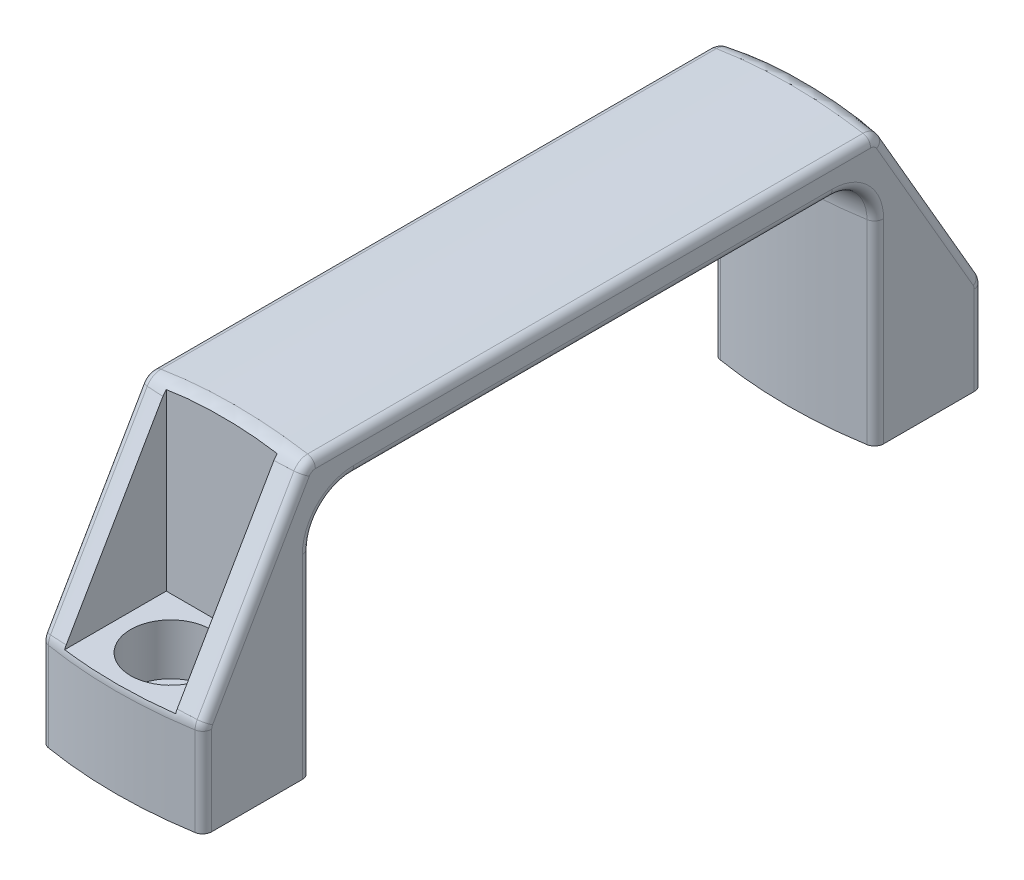
SolidWorks part; units mm, degrees
material "Nylon 6/10"
ref_plane "Front Plane" through (0, 0, 0) normal (0, 0, 1) x (1, 0, 0)
ref_plane "Top Plane" through (0, 0, 0) normal (0, 1, 0) x (1, 0, 0)
ref_plane "Right Plane" through (0, 0, 0) normal (1, 0, 0) x (0, 0, -1)
ref_axis "Axis1" through (0, 0, -88.99) along (0, 0, 1)
ref_axis "Axis2" through (0, -55, 0) along (0, 1, 0)
ref_axis "Axis3" through (-88.99, 0, 0) along (1, 0, 0)
sketch "Sketch1" plane through (0, 0, 0) normal (1, 0, 0) x (0, 0, -1)
  line L0 (-54.3719, 0) -> (-37.8312, 0)
  line L1 (-37.8312, 0) -> (-37.8312, 31.75)
  line L2 (-37.8312, 31.75) -> (0, 31.75)
  line L3 (0, 31.75) -> (0, 38.1)
  line L4 (0, 38.1) -> (-39.8313, 38.1)
  line L5 (-54.3719, 0) -> (-54.3719, 13)
  line L6 (-54.3719, 13) -> (-39.8313, 38.1)
  line L7 (-46.8313, 26.0166) -> (-46.8313, 0) construction
  line L8 (0, 0) -> (0, 31.75) construction
  line L9 (-49.8313, 20.838) -> (-49.8312, 0) construction
  line L10 (-43.8313, 31.1952) -> (-43.8313, 0) construction
  line L11 (-39.8313, 38.1) -> (-39.8313, 13)
  line L12 (-39.8313, 13) -> (-54.3719, 13)
  dimension "D1" = 6.35
  dimension "D2" = 38.1
  dimension "D3" = 93.6625
  dimension "D4" = 108.7438
  dimension "D5" = 6
  dimension "D6" = 13
  dimension "D7" = 2
  dimension "D8" = 4
extrude "Boss-Extrude1" add sketch "Sketch1" along normal mid plane 22.225 contours L11 L12 L5 L0 L1 L2 L3 L4 | L12 L11 L6 region at (0, 6.5, 53.708) region at (0, 21.3667, 44.6781)
extrude "Cut-Extrude1" cut sketch "Sketch1<3>" along normal offset from surface 3.5 and the other way offset from surface 3.5 contours L12 L11 L6 region at (0, 21.3667, 44.6781) up to face at (11.1125, 21.8143, 32.0339) other way up to face at (-11.1125, 21.8143, 32.0339)
sketch "Sketch1<3>" plane through (0, 0, 0) normal (1, 0, 0) x (0, 0, -1) same geometry as "Sketch1"
fillet "Fillet1" radius 5 1 edges at (0, 31.75, 37.8312)
hole_wizard "CBORE for  SHCS1" positions "Sketch3" profile "Sketch2" counterbore size "M6" standard "ANSI Metric" end condition through all
sketch "Sketch3" plane through (0, 13, 0) normal (0, 1, 0) x (1, 0, 0)
  point P0 (0, -46.8313)
sketch "Sketch2" plane through (0, 13, 46.8313) normal (1, 0, 0) x (0, 0, 1)
  line L0 (0, 0) -> (0, 13)
  line L1 (0, 13) -> (3.2, 13)
  line L3 (3.2, 13) -> (3.2, 7)
  line L4 (3.2, 7) -> (5.5, 7)
  line L5 (5.5, 7) -> (5.5, 0)
  line L7 (5.5, 0) -> (0, 0)
  line L11 (0, -6.35) -> (0, 107.95) construction
  dimension "Thru Hole Dia." = 6.4
  dimension "Thru Hole Depth" = 13
  dimension "C'Bore Dia." = 11
  dimension "C'Bore Depth" = 7
sketch "Sketch4" plane through (0, 0, 0) normal (0, 0, -1) x (-1, 0, 0)
  line L0 (-11.1125, 38.1) -> (11.1125, 38.1) construction
  line L1 (-11.1125, 37.1) -> (-11.1125, 48.1)
  line L2 (-11.1125, 31.75) -> (-11.1125, 38.1) construction
  line L3 (-11.1125, 48.1) -> (11.1125, 48.1)
  line L4 (11.1125, 48.1) -> (11.1125, 37.1)
  line L5 (11.1125, 31.75) -> (11.1125, 38.1) construction
  arc A0 (11.1125, 37.1) -> (-11.1125, 37.1) centre (0, -24.1438) ccw
  dimension "D1" = 10
  dimension "D2" = 1
sketch "Sketch5" plane through (0, 0, 0) normal (1, 0, 0) x (0, 0, -1)
  line L0 (0, 38.1) -> (-38.1021, 38.1)
  line L1 (0, 38.1) -> (-39.8313, 38.1) construction
  line L2 (-40.698, 36.6038) -> (-53.9677, 13.6976)
  line L3 (-54.3719, 12.1938) -> (-54.3719, 0)
  arc A0 (-38.1021, 38.1) -> (-40.698, 36.6038) centre (-38.1021, 35.1) ccw
  arc A1 (-53.9677, 13.6976) -> (-54.3719, 12.1938) centre (-51.3719, 12.1938) ccw
  point P12 (-39.8313, 38.1)
  point P15 (-54.3719, 13)
  dimension "D1" = 3
sweep "Cut-Sweep1" cut profiles "Sketch4" path "Sketch5"
sketch "Sketch6" plane through (0, 0, 0) normal (0, 0, -1) x (-1, 0, 0)
  line L0 (-11.1125, 30.75) -> (-11.1125, 32.75)
  line L1 (-11.1125, 31.75) -> (11.1125, 31.75) construction
  line L2 (-11.1125, 31.75) -> (-11.1125, 37.1) construction
  line L3 (11.1125, 32.75) -> (11.1125, 30.75)
  line L4 (-11.1125, 30.75) -> (11.1125, 30.75)
  line L5 (11.1125, 31.75) -> (11.1125, 37.1) construction
  arc A0 (-11.1125, 32.75) -> (11.1125, 32.75) centre (0, 93.9938) ccw
  dimension "D1" = 1
  dimension "D2" = 2
sketch "Sketch7" plane through (0, 0, 0) normal (1, 0, 0) x (0, 0, -1)
  line L0 (-32.8312, 31.75) -> (0, 31.75) construction
  line L1 (-37.8312, 0) -> (-37.8312, 26.75) construction
  line L2 (-32.8312, 31.75) -> (0, 31.75)
  line L3 (-37.8312, 0) -> (-37.8312, 26.75)
  arc A0 (-32.8312, 31.75) -> (-37.8312, 26.75) centre (-32.8312, 26.75) ccw construction
  arc A1 (-32.8312, 31.75) -> (-37.8312, 26.75) centre (-32.8312, 26.75) ccw
sweep "Cut-Sweep3" cut profiles "Sketch6" path "Sketch7"
fillet "Fillet2" radius 1.25 16 edges at (-11.1125, 32.75, 16.4156) (-11.1125, 30.9926, 37.0739) (11.1125, 32.75, 16.4156) (11.1125, 30.9926, 37.0739) (-11.1125, 13.375, 38.8312) (11.1125, 13.375, 38.8312) (11.1125, 6.0969, 53.3719) (11.1125, 12.7128, 53.3033) (11.1125, 24.6494, 46.4676) (11.1125, 36.8328, 39.1009) (-11.1125, 6.0969, 53.3719) (-11.1125, 12.7128, 53.3033) (-11.1125, 24.6494, 46.4676) (-11.1125, 36.8328, 39.1009) (11.1125, 37.1, 19.0511) (-11.1125, 37.1, 19.0511)
mirror "Mirror1" about plane through (0, 0, 0) normal (0, 0, 1) of bodies 105
